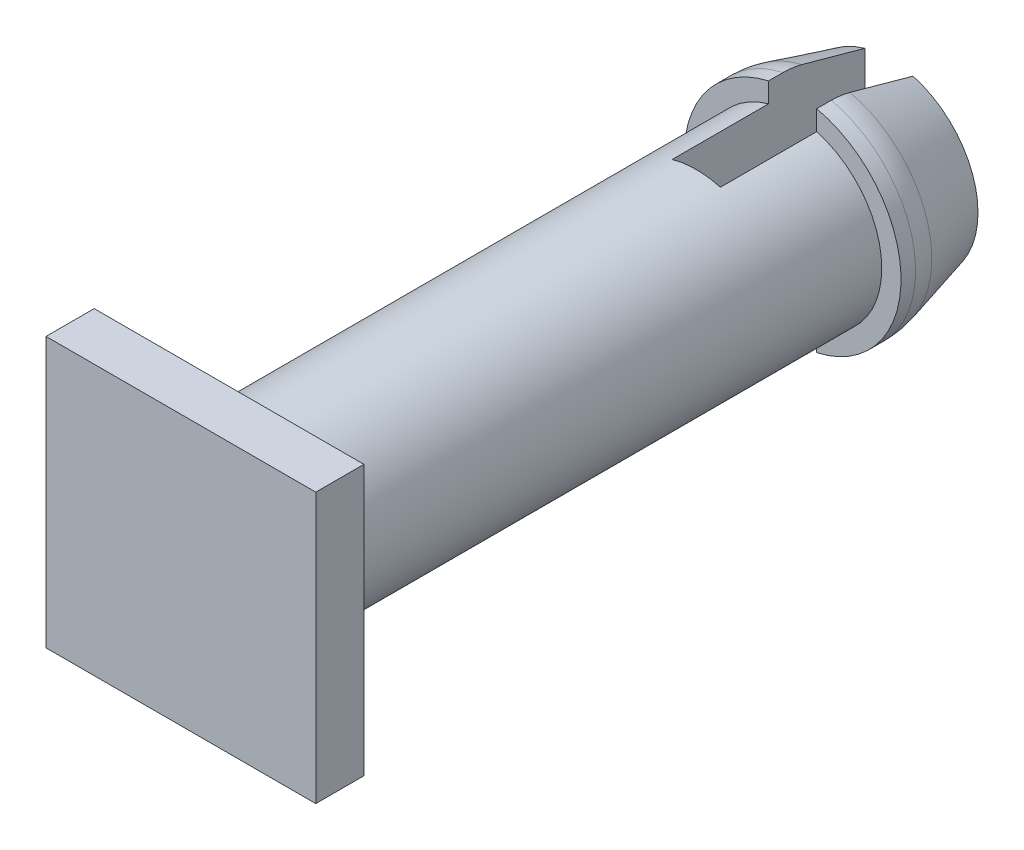
SolidWorks part; units mm, degrees
ref_plane "Front Plane" through (0, 0, 0) normal (0, 0, 1) x (1, 0, 0)
ref_plane "Top Plane" through (0, 0, 0) normal (0, 1, 0) x (1, 0, 0)
ref_plane "Right Plane" through (0, 0, 0) normal (1, 0, 0) x (0, 0, -1)
sketch "Sketch1" plane through (0, 0, 0) normal (0, 0, 1) x (1, 0, 0)
  line L1 (-2.8, 2.8) -> (2.8, 2.8)
  line L2 (-2.8, 2.8) -> (-2.8, -2.8)
  line L3 (-2.8, -2.8) -> (2.8, -2.8)
  line L4 (2.8, 2.8) -> (2.8, -2.8)
  line L5 (-2.8, 2.8) -> (2.8, -2.8) construction
  line L6 (-2.8, -2.8) -> (2.8, 2.8) construction
  circle A0 centre (0, 0) radius 1.85
  point P0 (0, 0)
  dimension "D2" = 3.7
  dimension "D1" = 5.6
extrude "Boss-Extrude1" add sketch "Sketch1" along normal blind 1 contours L4 L3 L2 L1
extrude "Boss-Extrude2" add sketch "Sketch1<3>" against normal blind 11.7 contours A0
sketch "Sketch1<3>" plane through (0, 0, 0) normal (0, 0, 1) x (1, 0, 0) same geometry as "Sketch1"
sketch "Sketch2" plane through (0, 0, -11.7) normal (0, 0, -1) x (-1, 0, 0)
  circle A0 centre (0, 0) radius 0.6
  dimension "D1" = 1.2
extrude "Cut-Extrude1" cut sketch "Sketch2" against normal blind 5
sketch "Sketch3" plane through (0, 0, -11.7) normal (0, 0, -1) x (-1, 0, 0)
  circle A0 centre (0, 0) radius 2.25
  circle A1 centre (0, 0) radius 0.6 construction
  circle A2 centre (0, 0) radius 0.6
  dimension "D1" = 4.5
extrude "Boss-Extrude3" add sketch "Sketch3" along normal blind 2
chamfer "Chamfer1" distance 1.5 angle 15 1 edges at (-2.25, 0, -13.7) first distance on face at (-2.25, 0, -13.7)
sketch "Sketch4" plane through (0, 0, -13.7) normal (0, 0, -1) x (-1, 0, 0)
  line L0 (2.8, -2.8) -> (-2.8, 2.8) construction
  line L1 (0.5, -2.6434) -> (-0.5, -2.6434)
  line L2 (0.5, -2.6434) -> (0.5, 2.6434)
  line L3 (0.5, 2.6434) -> (-0.5, 2.6434)
  line L4 (-0.5, -2.6434) -> (-0.5, 2.6434)
  line L5 (0.5, -2.6434) -> (-0.5, 2.6434) construction
  line L6 (0.5, 2.6434) -> (-0.5, -2.6434) construction
  point P0 (0, 0)
  dimension "D1" = 1
extrude "Cut-Extrude3" cut sketch "Sketch4" against normal blind 4
fillet "Fillet1" radius 1.5 2 edges at (2.25, 0, -12.2) (-2.25, 0, -12.2)
